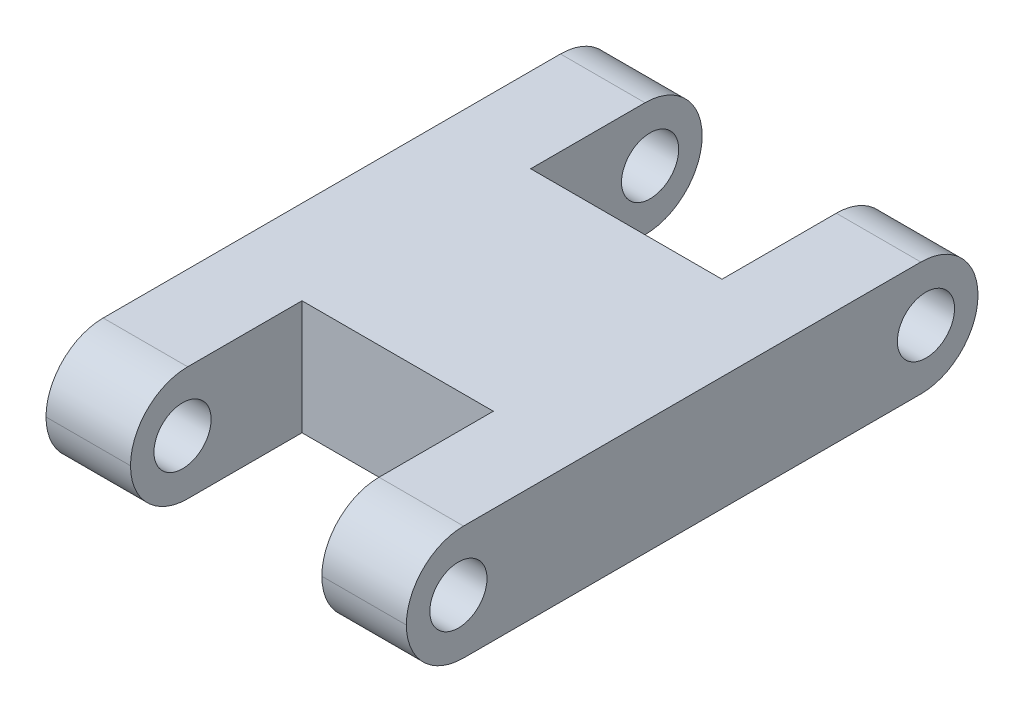
SolidWorks part; units mm, degrees
ref_plane "Plan de face" through (0, 0, 0) normal (0, 0, 1) x (1, 0, 0)
ref_plane "Plan de dessus" through (0, 0, 0) normal (0, 1, 0) x (1, 0, 0)
ref_plane "Plan de droite" through (0, 0, 0) normal (1, 0, 0) x (0, 0, -1)
sketch "Esquisse1" plane through (0, 0, 0) normal (0, 1, 0) x (1, 0, 0)
  line L0 (0, 0) -> (0, -50)
  line L1 (0, -50) -> (7.3922, -50)
  line L2 (7.3922, -50) -> (7.3922, -35)
  line L3 (7.3922, -35) -> (24.1278, -35)
  line L4 (15.76, -35) -> (15.76, -15)
  line L5 (24.1278, -15) -> (7.3922, -15)
  line L6 (7.3922, -15) -> (7.3922, 0)
  line L7 (7.3922, 0) -> (0, 0)
  line L8 (15.76, 193.3046) -> (15.76, 58.3037) construction
  line L9 (24.1278, 0) -> (31.52, 0)
  line L10 (24.1278, -15) -> (24.1278, 0)
  line L11 (24.1278, -50) -> (24.1278, -35)
  line L12 (31.52, -50) -> (24.1278, -50)
  line L13 (31.52, 0) -> (31.52, -50)
  dimension "D1" = 50
  dimension "D2" = 15
  dimension "D3" = 15
extrude "Boss.-Extru.1" add sketch "Esquisse1" along normal blind 10 contours L6 L7 L0 L1 L2 L3 L4 L5 | L13 L9 L10 L5 L4 L3 L11 L12 region at (6.1521, 0, 25) region at (25.368, 0, 25)
fillet "Congé1" radius 5 8 edges at (27.8239, 0, 50) (3.6961, 0, 50) (3.6961, 10, 50) (27.8239, 10, 50) (27.8239, 10, 0) (27.8239, 0, 0) (3.6961, 0, 0) (3.6961, 10, 0)
sketch "Esquisse2" plane through (0, 0, 0) normal (-1, 0, 0) x (0, 0, 1)
  line L2 (5, 0) -> (45, 0) construction
  line L4 (25, 0) -> (25, 10) construction
  line L5 (5, 10) -> (45, 10) construction
  circle A0 centre (4.5522, 5) radius 2.5
  circle A1 centre (45.4478, 5) radius 2.5
  dimension "D1" = 5
extrude "Enlèv. mat.-Extru.1" cut sketch "Esquisse2" against normal blind 50
